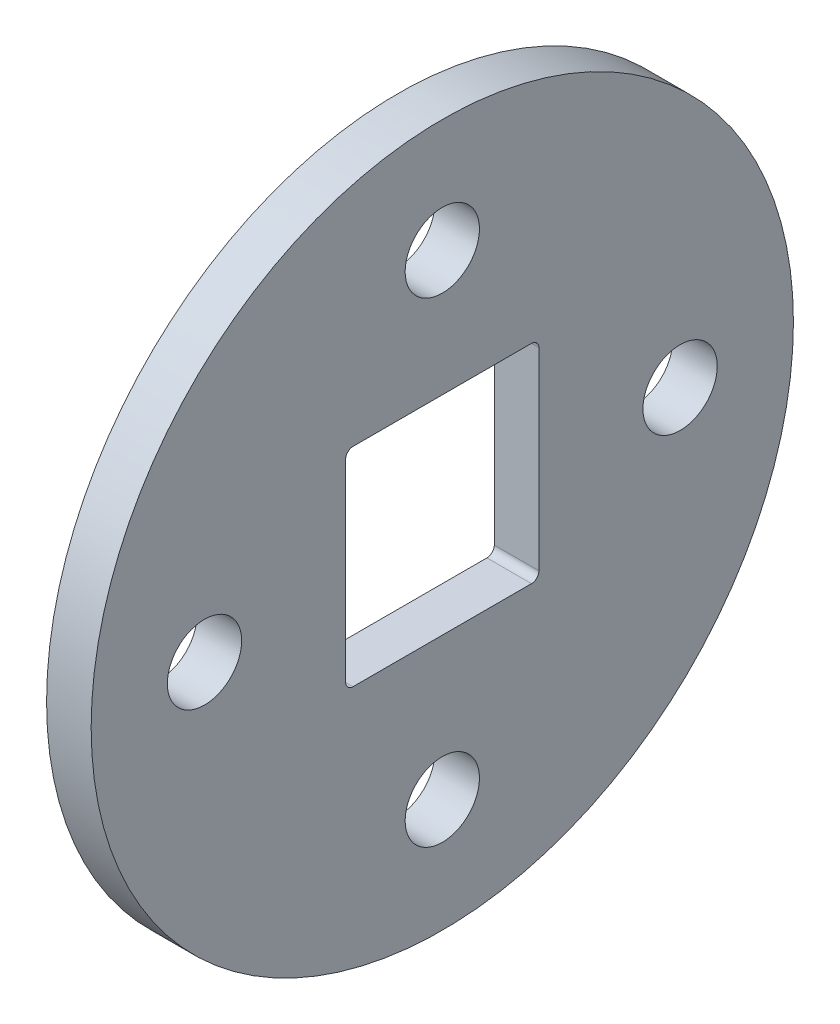
SolidWorks part; units mm, degrees
note: '?' marks a value the reader was unsure of.
material "50% - PLA"
ref_plane "Front Plane" through (0, 0, 0) normal (0, 0, 1) x (1, 0, 0)
ref_plane "Top Plane" through (0, 0, 0) normal (0, 1, 0) x (1, 0, 0)
ref_plane "Right Plane" through (0, 0, 0) normal (1, 0, 0) x (0, 0, -1)
sketch "Sketch1" plane through (0, 0, 0) normal (1, 0, 0) x (0, 0, -1)
  circle A0 centre (0, 0) radius 47.25
  dimension "D2" = 94.5
extrude "Boss-Extrude1" add sketch "Sketch1" along normal blind 6
sketch "Sketch2" plane through (6, 0, 0) normal (1, 0, 0) x (0, 0, -1)
  line L0 (12, -12.85) -> (-12, -12.85)
  line L1 (13, -3.85) -> (13, -11.85)
  line L2 (12, -11.85) -> (-12, -11.85)
  line L3 (-13, -11.85) -> (-13, -3.85)
  line L4 (-13, -3.85) -> (-13, 14.15)
  line L5 (13, -3.85) -> (13, 14.15)
  line L6 (12, 15.15) -> (-12, 15.15)
  line L7 (12, -12.85) -> (-12, -12.85) construction
  arc A0 (13, -11.85) -> (12, -12.85) centre (12, -11.85) cw
  arc A1 (-13, -11.85) -> (-12, -12.85) centre (-12, -11.85) ccw
  arc A4 (12, -11.85) -> (13, -10.85) centre (12, -10.85) ccw
  arc A5 (-13, -10.85) -> (-12, -11.85) centre (-12, -10.85) ccw
  arc A8 (-13, 14.15) -> (-12, 15.15) centre (-12, 14.15) cw
  arc A9 (13, 14.15) -> (12, 15.15) centre (12, 14.15) ccw
  point P26 (13, 15.15)
  dimension "D2" = 1
  dimension "D4" = 1
  dimension "D1" = 19
  dimension "D3" = 1
extrude "Cut-Extrude1" cut sketch "Sketch2" against normal blind 20 contours A5 L3 A1 L0 A0 L1 A4 L2 | L5 A9 L6 A8 L4 L3 A5 L2 A4 L1
sketch "Sketch3" plane through (6, 0, 0) normal (1, 0, 0) x (0, 0, -1)
  line L0 (0, 0) -> (-33.4108, 33.4108)
  line L1 (-33.4108, 33.4108) -> (33.4108, -33.4108)
  line L2 (0, 0) -> (33.4108, 33.4108)
  line L3 (0, 0) -> (-33.4108, -33.4108)
  circle A0 centre (0, 0) radius 47.25 construction
ref_plane "Plane1" through (0, 33.4108, 33.4108) normal (0, 0.7071, 0.7071) x (-1, 0, 0)
ref_plane "Plane2" through (0, -33.4108, 33.4108) normal (0, -0.7071, 0.7071) x (-1, 0, 0)
ref_plane "Plane3" through (0, 33.4108, -33.4108) normal (0, 0.7071, -0.7071) x (-1, 0, 0)
ref_plane "Plane4" through (0, -33.4108, -33.4108) normal (0, -0.7071, -0.7071) x (-1, 0, 0)
hole_wizard "Ø6.0mm Dowel Hole1" [suppressed] positions "Sketch5" profile "Sketch4" hole size "Ø6.0" standard "ISO"
sketch "Sketch5" plane through (0, 33.4108, 33.4108) normal (0, 0.7071, 0.7071) x (-1, 0, 0)
  line L0 (-6, 0) -> (-6, 47.25) construction
  point P0 (1.5, 0)
  dimension "D1" = 7.5
sketch "Sketch4" plane through (-1.5, 33.4108, 33.4108) normal (1, 0, 0) x (0, -0.7071, 0.7071)
  line L0 (0, 0) -> (0, 17.8026)
  line L1 (0, 17.8026) -> (3, 16)
  line L2 (3, 16) -> (3, 0)
  line L5 (3, 0) -> (0, 0)
  line L10 (0, 17.8026) -> (-3, 16) construction
  line L11 (0, -6.35) -> (0, 107.95) construction
  dimension "Hole Dia." = 6
  dimension "Hole Depth" = 16
  dimension "Drill Angle" = 118
hole_wizard "Ø6.0mm Dowel Hole2" [suppressed] positions "Sketch7" profile "Sketch6" hole size "Ø6.0" standard "ISO"
sketch "Sketch7" plane through (0, -33.4108, 33.4108) normal (0, -0.7071, 0.7071) x (-1, 0, 0)
  line L0 (-6, 0) -> (-6, -47.25) construction
  point P0 (1.5, 0)
  dimension "D1" = 7.5
sketch "Sketch6" plane through (-1.5, -33.4108, 33.4108) normal (1, 0, 0) x (0, -0.7071, -0.7071)
  line L0 (0, 0) -> (0, 17.8026)
  line L1 (0, 17.8026) -> (3, 16)
  line L2 (3, 16) -> (3, 0)
  line L5 (3, 0) -> (0, 0)
  line L10 (0, 17.8026) -> (-3, 16) construction
  line L11 (0, -6.35) -> (0, 107.95) construction
  dimension "Hole Dia." = 6
  dimension "Hole Depth" = 16
  dimension "Drill Angle" = 118
hole_wizard "Ø6.0mm Dowel Hole3" [suppressed] positions "Sketch9" profile "Sketch8" hole size "Ø6.0" standard "ISO"
sketch "Sketch9" plane through (0, -33.4108, -33.4108) normal (0, -0.7071, -0.7071) x (-1, 0, 0)
  line L0 (-6, 0) -> (-6, -47.25) construction
  point P0 (1.5, 0)
  dimension "D1" = 7.5
sketch "Sketch8" plane through (-1.5, -33.4108, -33.4108) normal (1, 0, 0) x (0, 0.7071, -0.7071)
  line L0 (0, 0) -> (0, 17.8026)
  line L1 (0, 17.8026) -> (3, 16)
  line L2 (3, 16) -> (3, 0)
  line L5 (3, 0) -> (0, 0)
  line L10 (0, 17.8026) -> (-3, 16) construction
  line L11 (0, -6.35) -> (0, 107.95) construction
  dimension "Hole Dia." = 6
  dimension "Hole Depth" = 16
  dimension "Drill Angle" = 118
hole_wizard "Ø6.0mm Dowel Hole4" [suppressed] positions "Sketch11" profile "Sketch10" hole size "Ø6.0" standard "ISO"
sketch "Sketch11" plane through (0, 33.4108, -33.4108) normal (0, 0.7071, -0.7071) x (-1, 0, 0)
  line L0 (0, -47.25) -> (0, 47.25) construction
  point P0 (-7.5, 0)
  dimension "D1" = 7.5
sketch "Sketch10" plane through (7.5, 33.4108, -33.4108) normal (1, 0, 0) x (0, 0.7071, 0.7071)
  line L0 (0, 0) -> (0, 17.8026)
  line L1 (0, 17.8026) -> (3, 16)
  line L2 (3, 16) -> (3, 0)
  line L5 (3, 0) -> (0, 0)
  line L10 (0, 17.8026) -> (-3, 16) construction
  line L11 (0, -6.35) -> (0, 107.95) construction
  dimension "Hole Dia." = 6
  dimension "Hole Depth" = 16
  dimension "Drill Angle" = 118
hole_wizard "CBORE for M5 Hex Socket Head Cap Screw2" positions "Sketch15" profile "Sketch14" counterbore size "M5" standard "ISO"
sketch "Sketch15" plane through (0, 0, 0) normal (-1, 0, 0) x (0, 0, 1)
  point P0 (-32, 0)
  point P8 (0, 32)
  point P9 (32, 0)
  point P10 (0, -32)
  dimension "D2" = 4
sketch "Sketch14" plane through (0, 0, -32) normal (0, 1, 0) x (0, 0, 1)
  line L0 (0, 0) -> (0, 21.5923)
  line L1 (0, 21.5923) -> (2.65, 20)
  line L2 (2.65, 20) -> (2.65, 15.4)
  line L3 (2.65, 15.4) -> (5, 15.4)
  line L4 (5, 15.4) -> (5, 0)
  line L5 (5, 0) -> (0, 0)
  line L10 (0, 21.5923) -> (-2.65, 20) construction
  line L11 (0, -6.35) -> (0, 107.95) construction
  dimension "Hole Dia." = 5.3
  dimension "Hole Depth" = 20
  dimension "C'Bore Dia." = 10
  dimension "C'Bore Depth" = 15.4
  dimension "Drill Angle" = 118
sketch "Sketch16" plane through (6, 0, 0) normal (1, 0, 0) x (0, 0, -1)
  line L0 (12, 15.15) -> (-12, 15.15) construction
  line L1 (19, 15.15) -> (-19, 15.15)
  line L2 (0, 15.15) -> (0, -4.85)
  line L3 (19, -4.85) -> (-19, -4.85)
  line L4 (-19, 15.15) -> (-19, -4.85)
  line L5 (19, 15.15) -> (19, -4.85)
  line M5 (13, 14.15) -> (13, -11.85)
  line M9 (-13, -11.85) -> (-13, 14.15)
  arc M10 (-13, 14.15) -> (-12, 15.15) centre (-12, 14.15) cw
  line M11 (-12, 15.15) -> (12, 15.15)
  arc M12 (12, 15.15) -> (13, 14.15) centre (12, 14.15) cw
  dimension "D1" = 19
  dimension "D2" = 20
extrude "Cut-Extrude2" [suppressed] cut sketch "Sketch16" against normal blind 1.5 contours L5 L1 L3 M12 M5 | L3 L1 L2 M5 M12 | L3 L2 M11 M10 M9 | L1 L4 L3 M9 M10
fillet "Fillet1" [suppressed] radius 1
ref_axis "Axis1" through (6, 0, 0) along (-1, 0, 0)?
